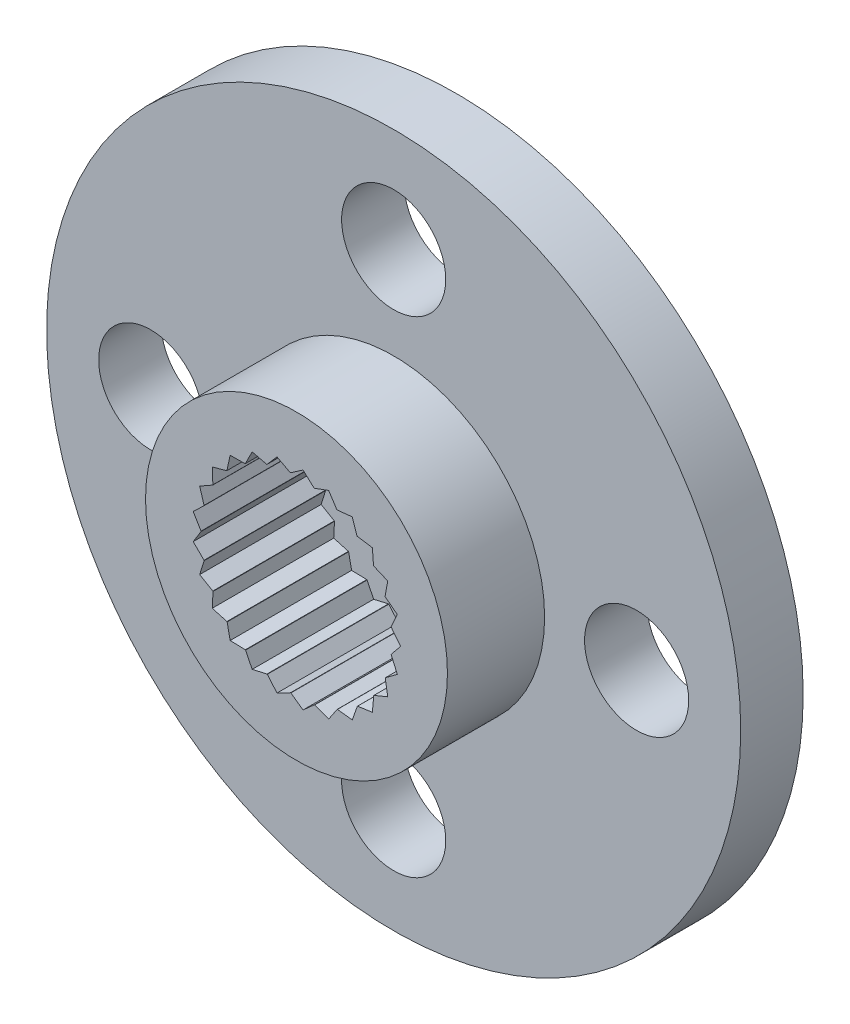
SolidWorks part; units mm, degrees
material "6061 Alloy"
ref_plane "Front Plane" through (0, 0, 0) normal (0, 0, 1) x (1, 0, 0)
ref_plane "Top Plane" through (0, 0, 0) normal (0, 1, 0) x (1, 0, 0)
ref_plane "Right Plane" through (0, 0, 0) normal (1, 0, 0) x (0, 0, -1)
sketch "Sketch1" plane through (0, 0, 0) normal (0, 0, 1) x (1, 0, 0)
  circle A0 centre (0, 0) radius 10
  circle A1 centre (0, 0) radius 7 construction
  circle A2 centre (0, 7) radius 1.5
  circle A3 centre (7, 0) radius 1.5
  circle A4 centre (0, -7) radius 1.5
  circle A5 centre (-7, 0) radius 1.5
  circle A6 centre (0, 0) radius 4.35
  dimension "D1" = 20
  dimension "D2" = 3
  dimension "D4" = 7
  dimension "D5" = 8.7
  dimension "D3" = 4
extrude "Boss-Extrude1" add sketch "Sketch1" along normal blind 1.8
extrude "Boss-Extrude2" add sketch "Sketch1<2>" along normal blind 4.6 contours A6 region at (0, 0, 0)
sketch "Sketch1<2>" plane through (0, 0, 0) normal (0, 0, 1) x (1, 0, 0) same geometry as "Sketch1"
sketch "Sketch2" plane through (0, 0, 0) normal (0, 0, -1) x (-1, 0, 0)
  circle A0 centre (0, 0) radius 1.5
extrude "Cut-Extrude1" cut sketch "Sketch2" against normal blind 4.5
sketch "Sketch3" plane through (0, 0, 4.6) normal (0, 0, 1) x (1, 0, 0)
  circle A0 centre (0, 0) radius 2.75
extrude "Cut-Extrude2" cut sketch "Sketch3" against normal blind 3.5
sketch "Sketch4" plane through (0, 0, 4.6) normal (0, 0, 1) x (1, 0, 0)
  line L0 (0, 0) -> (-3, 0)
  line L1 (0, 0) -> (-2.9763, 0.376)
  line L2 (0, 0) -> (-2.9083, 0.7359)
  line L3 (-2.75, 0) -> (-2.9763, 0.376)
  line L4 (-2.666, 0.6746) -> (-2.9763, 0.376)
  circle A0 centre (0, 0) radius 3
  circle A1 centre (0, 0) radius 2.75 construction
  circle A2 centre (0, 0) radius 2.75 construction
  circle A3 centre (0, 0) radius 2.75
  circle M6 centre (0, 0) radius 2.75
  dimension "D1" = 7.2
  dimension "D2" = 14.2
extrude "Cut-Extrude3" cut sketch "Sketch4" against normal blind 3.5 contours L4 L1 M6 | L3 L1 M6 region at (-2.8205, 0.2422, 4.6) region at (-2.7928, 0.4638, 4.6)
pattern_circular "CirPattern1" count 25 over 360 about axis through (0, 0, 4.5) along (0, 0, -1) of "Cut-Extrude3" reverse direction yes
